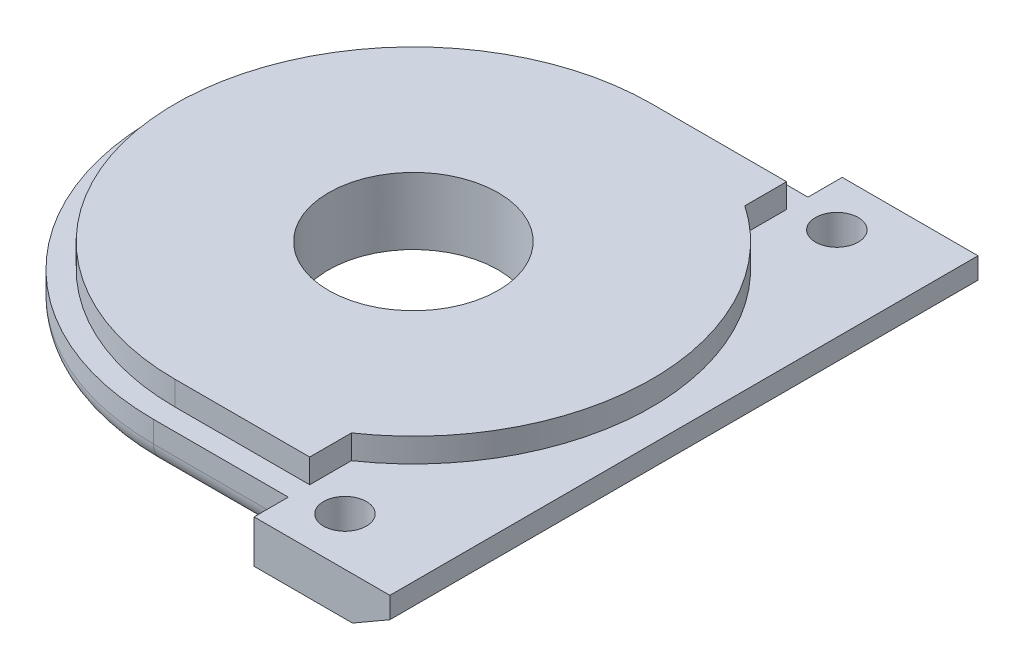
SolidWorks part; units mm, degrees
material "6061-T6 (SS)"
ref_plane "Front Plane" through (0, 0, 0) normal (0, 0, 1) x (1, 0, 0)
ref_plane "Top Plane" through (0, 0, 0) normal (0, 1, 0) x (1, 0, 0)
ref_plane "Right Plane" through (0, 0, 0) normal (1, 0, 0) x (0, 0, -1)
sketch "Sketch1" plane through (0, 0, 0) normal (0, 1, 0) x (1, 0, 0)
  line L0 (-13.2912, 20.8898) -> (-0.69, 20.8898)
  line L2 (-0.69, 24.0921) -> (-0.69, 20.8898)
  line L4 (12.01, 24.0921) -> (12.01, -26.9079)
  line L5 (-13.2912, -23.7056) -> (-0.69, -23.7056)
  line L6 (-0.69, -23.7056) -> (-0.69, -26.9079)
  line L13 (-0.69, -28.9079) -> (-0.69, -26.9079)
  line L15 (12.01, -28.9079) -> (12.01, -26.9079)
  line L16 (12.01, -28.9079) -> (-0.69, -28.9079)
  line L18 (12.01, 26.0921) -> (12.01, 24.0921)
  line L20 (-0.69, 26.0921) -> (-0.69, 24.0921)
  line L21 (-0.69, 26.0921) -> (12.01, 26.0921)
  arc A0 (-13.2912, 20.8898) -> (-13.2912, -23.7056) centre (-13.2912, -1.4079) ccw
extrude "Boss-Extrude1" add sketch "Sketch1" along normal blind 4
sketch "Sketch2" plane through (0, 4, 0) normal (0, 1, 0) x (1, 0, 0)
  line L0 (-0.69, 20.8898) -> (-0.69, 16.9877)
  line L1 (-0.69, -23.7056) -> (-0.69, -19.8035)
  line L2 (-0.69, -23.7056) -> (-13.2912, -23.7056)
  line L3 (-0.69, 20.8898) -> (-13.2912, 20.8898)
  arc A0 (-0.69, -19.8035) -> (-0.69, 16.9877) centre (-13.2912, -1.4079) ccw
  arc A1 (-13.2912, 20.8898) -> (-13.2912, -23.7056) centre (-13.2912, -1.4079) ccw
extrude "Boss-Extrude2" add sketch "Sketch2" along normal blind 2.25
sketch "Sketch3" plane through (0, 0, 0) normal (0, -1, 0) x (1, 0, 0)
  circle A0 centre (-13.2912, 1.4079) radius 7.925
  dimension "D1" = 15.85
extrude "Cut-Extrude1" cut sketch "Sketch3" against normal blind 9.25
sketch "Sketch4" plane through (0, 0, 0) normal (0, -1, 0) x (1, 0, 0)
  line L0 (-0.69, -26.0921) -> (3.31, -26.0921) construction
  line L1 (12.01, -26.0921) -> (-0.69, -26.0921) construction
  line L3 (3.31, -26.0921) -> (3.31, -21.5921) construction
  line L4 (-0.69, 28.9079) -> (3.31, 28.9079) construction
  line L5 (3.31, 28.9079) -> (3.31, 24.4079) construction
  circle A2 centre (3.31, -21.5921) radius 2
  circle A3 centre (3.31, 24.4079) radius 2
extrude "Cut-Extrude2" cut sketch "Sketch4" against normal blind 9.25
sketch "Sketch5" plane through (0, 0, 0) normal (0, -1, 0) x (1, 0, 0)
  line L9 (-20.9013, 10.589) -> (-24.2357, 16.3644)
  line L12 (-17.4372, 12.589) -> (-20.7716, 18.3644)
  line L14 (-1.5351, 3.4079) -> (5.1338, 3.4079)
  line L17 (-1.5351, -0.5921) -> (5.1338, -0.5921)
  line L19 (-17.4372, -9.7732) -> (-20.7716, -15.5486)
  line L22 (-20.9013, -7.7732) -> (-24.2357, -13.5486)
  circle A2 centre (-13.2912, 1.4079) radius 11.925
  arc A3 (-1.5351, 3.4079) -> (-17.4372, 12.589) centre (-13.2912, 1.4079) ccw
  circle A4 centre (-13.2912, 1.4079) radius 18.425
  circle A5 centre (-13.2912, 1.4079) radius 18.425
  circle A6 centre (-13.2912, 1.4079) radius 18.425
  circle A7 centre (-13.2912, 1.4079) radius 18.425
  arc A8 (-20.9013, 10.589) -> (-20.9013, -7.7732) centre (-13.2912, 1.4079) ccw
  arc A9 (-17.4372, -9.7732) -> (-1.5351, -0.5921) centre (-13.2912, 1.4079) ccw
  point P14 (-13.2912, 1.4079)
  dimension "D1" = 4
  dimension "D2" = 10.5
  dimension "D3" = 3
extrude "Cut-Extrude3" cut sketch "Sketch5" against normal blind 3 contours A8 L9 A4 L22 | L14 A4 L12 A3 | A9 L19 A4 L17 region at (-26.6554, 0, 1.4079) region at (-6.6091, 0, 12.9816) region at (-6.6091, 0, -10.1658)
fillet "Fillet1" radius 2.36 12 edges at (5.0249, 1.5, 3.4079) (-1.5351, 1.5, 3.4079) (5.0249, 1.5, -0.5921) (-24.1813, 1.5, 16.2701) (-20.7172, 1.5, 18.2701) (-1.5351, 1.5, -0.5921) (-20.7172, 1.5, -15.4543) (-20.9013, 1.5, 10.589) (-20.9013, 1.5, -7.7732) (-24.1813, 1.5, -13.4543) (-17.4372, 1.5, -9.7732) (-17.4372, 1.5, 12.589)
chamfer "Chamfer1" distance 3.5 angle 30 1 edges at (12.01, 0, 1.4079) first distance on face at (-7.8389, 0, -8.0358)
sketch "Sketch6" plane through (0, 0, 0) normal (0, -1, 0) x (1, 0, 0)
  line L2 (-0.69, -22.8898) -> (-13.2912, -22.8898)
  line L3 (-13.2912, 25.7056) -> (-0.69, 25.7056)
  line L4 (-0.69, -20.8898) -> (-13.2912, -20.8898)
  line L5 (-13.2912, 23.7056) -> (-0.69, 23.7056)
  line L6 (-0.69, -20.8898) -> (-13.2912, -20.8898)
  line L7 (-13.2912, 23.7056) -> (-0.69, 23.7056)
  line L8 (-0.69, 25.7056) -> (-0.69, 23.7056)
  line L9 (-0.69, -20.8898) -> (-0.69, -22.8898)
  arc A1 (-13.2912, 25.7056) -> (-13.2912, -22.8898) centre (-13.2912, 1.4079) ccw
  arc A2 (-13.2912, 23.7056) -> (-13.2912, -20.8898) centre (-13.2912, 1.4079) ccw
  arc A3 (-13.2912, 23.7056) -> (-13.2912, -20.8898) centre (-13.2912, 1.4079) ccw
  dimension "D1" = 0
  dimension "D2" = 2
extrude "Boss-Extrude3" add sketch "Sketch6" against normal blind 4
fillet "Fillet2" radius 2 3 edges at (-6.9906, 0, 25.7056) (-6.9906, 0, -22.8898) (-37.5889, 0, 1.4079)
ref_axis "Axis2" through (-13.2912, 6.25, 1.4079) along (0, -1, 0)
